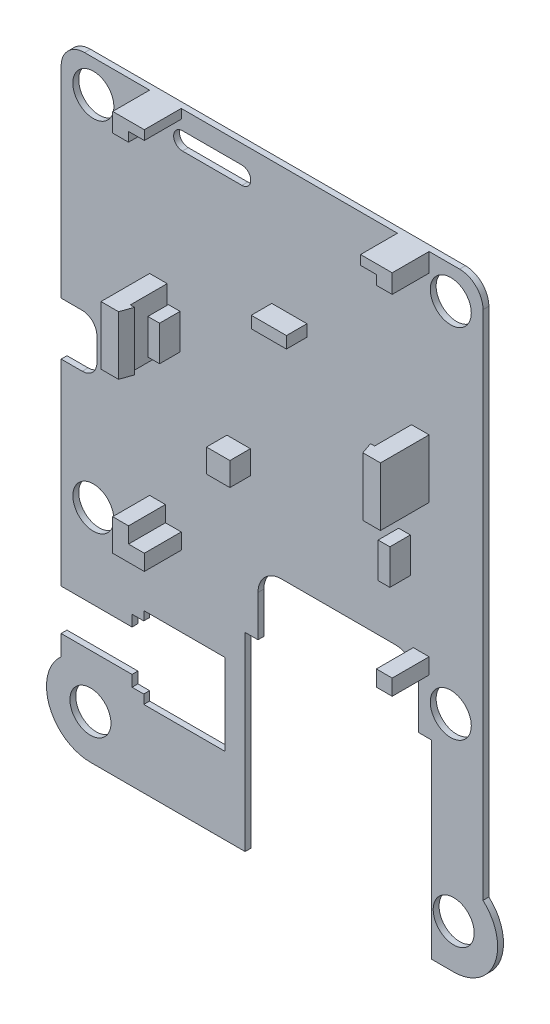
SolidWorks part; units mm, degrees
ref_plane "Front Plane" through (0, 0, 0) normal (0, 0, 1) x (1, 0, 0)
ref_plane "Top Plane" through (0, 0, 0) normal (0, 1, 0) x (1, 0, 0)
ref_plane "Right Plane" through (0, 0, 0) normal (1, 0, 0) x (0, 0, -1)
sketch "Sketch1" plane through (0, 0, 0) normal (0, 0, 1) x (1, 0, 0)
  line L9 (18, -18) -> (-18, -18)
  line L14 (16, 18) -> (-16, 18)
  line L15 (-18, 16) -> (-18, -1.15)
  line L16 (-18, -1.15) -> (-16.2, -1.15)
  line L17 (-14.95, -2.4) -> (-14.95, -4.4)
  line L18 (-16.2, -5.65) -> (-18, -5.65)
  line L19 (-18, -5.65) -> (-18, -18)
  line L20 (-18, -18) -> (-1.2, -18)
  line L21 (-1.2, -18) -> (-1.2, -14.5)
  line L22 (0.8, -12.5) -> (10.5, -12.5)
  line L23 (12.5, -14.5) -> (12.5, -18)
  line L24 (12.5, -18) -> (18, -18)
  line L25 (18, -18) -> (18, 16)
  line L26 (16, 18) -> (-16, 18)
  line L27 (-18, 16) -> (-18, -1.15)
  line L28 (-18, -1.15) -> (-16.2, -1.15)
  line L29 (-14.95, -2.4) -> (-14.95, -4.4)
  line L30 (-16.2, -5.65) -> (-18, -5.65)
  line L31 (-18, -5.65) -> (-18, -18)
  line L32 (-18, -18) -> (-1.2, -18)
  line L33 (-1.2, -18) -> (-1.2, -14.5)
  line L34 (0.8, -12.5) -> (10.5, -12.5)
  line L35 (12.5, -14.5) -> (12.5, -18)
  line L36 (12.5, -18) -> (18, -18)
  line L37 (18, -18) -> (18, 16)
  line L41 (13.6, -18) -> (13.6, -34.2)
  line L42 (13.6, -34.2) -> (15.5, -34.2)
  line L43 (18, -27.6549) -> (18, -18)
  line L44 (18, -18) -> (13.6, -18)
  line L46 (13.6, -18) -> (13.6, -34.2)
  line L47 (13.6, -34.2) -> (15.5, -34.2)
  line L48 (18, -27.6549) -> (18, -18)
  line L49 (18, -18) -> (13.6, -18)
  line L66 (-2.3, -18) -> (-18, -18)
  line L153 (-11.95, -22.43) -> (-11.95, -21.48)
  line L154 (-11.95, -21.48) -> (-10.95, -21.48)
  line L155 (-10.95, -21.48) -> (-10.95, -20.71)
  line L156 (-10.95, -20.71) -> (-4.01, -20.71)
  line L157 (-4.01, -20.71) -> (-4.01, -27.65)
  line L158 (-4.01, -27.65) -> (-10.95, -27.65)
  line L159 (-10.95, -27.65) -> (-10.95, -26.88)
  line L160 (-10.95, -26.88) -> (-11.95, -26.88)
  line L161 (-11.95, -26.88) -> (-11.95, -25.93)
  line L162 (-11.95, -25.93) -> (-18, -25.93)
  line L163 (-18, -25.93) -> (-18, -27.6549)
  line L164 (-15.5, -34.2) -> (-2.3, -34.2)
  line L165 (-2.3, -34.2) -> (-2.3, -18)
  line L166 (-2.3, -18) -> (-18, -18)
  line L167 (-18, -18) -> (-18, -22.43)
  line L168 (-18, -22.43) -> (-11.95, -22.43)
  line L169 (-11.95, -22.43) -> (-11.95, -21.48)
  line L170 (-11.95, -21.48) -> (-10.95, -21.48)
  line L171 (-10.95, -21.48) -> (-10.95, -20.71)
  line L172 (-10.95, -20.71) -> (-4.01, -20.71)
  line L173 (-4.01, -20.71) -> (-4.01, -27.65)
  line L174 (-4.01, -27.65) -> (-10.95, -27.65)
  line L175 (-10.95, -27.65) -> (-10.95, -26.88)
  line L176 (-10.95, -26.88) -> (-11.95, -26.88)
  line L177 (-11.95, -26.88) -> (-11.95, -25.93)
  line L178 (-11.95, -25.93) -> (-18, -25.93)
  line L179 (-18, -25.93) -> (-18, -27.6549)
  line L180 (-15.5, -34.2) -> (-2.3, -34.2)
  line L181 (-2.3, -34.2) -> (-2.3, -18)
  line L182 (-2.3, -18) -> (-18, -18)
  line L183 (-18, -18) -> (-18, -22.43)
  line L184 (-18, -22.43) -> (-11.95, -22.43)
  line L229 (-7.65, 14.9) -> (-2.57, 14.9) construction
  line L230 (-7.65, 16.4) -> (-2.57, 16.4) construction
  line L231 (-7.65, 16.4) -> (-2.57, 16.4)
  line L232 (-7.65, 14.9) -> (-2.57, 14.9)
  circle A2 centre (15.5, -30.45) radius 1.75 construction
  arc A3 (15.5, -34.2) -> (18, -27.6549) centre (15.5, -30.45) ccw
  circle A4 centre (15.25, -15.25) radius 1.75 construction
  circle A5 centre (15.25, 15.25) radius 1.75 construction
  circle A6 centre (-15.25, -15.25) radius 1.75 construction
  arc A7 (-16, 18) -> (-18, 16) centre (-16, 16) ccw
  arc A8 (-14.95, -2.4) -> (-16.2, -1.15) centre (-16.2, -2.4) ccw
  arc A9 (-16.2, -5.65) -> (-14.95, -4.4) centre (-16.2, -4.4) ccw
  arc A10 (0.8, -12.5) -> (-1.2, -14.5) centre (0.8, -14.5) ccw
  arc A11 (12.5, -14.5) -> (10.5, -12.5) centre (10.5, -14.5) ccw
  arc A12 (18, 16) -> (16, 18) centre (16, 16) ccw
  arc A14 (-16, 18) -> (-18, 16) centre (-16, 16) ccw
  arc A15 (-14.95, -2.4) -> (-16.2, -1.15) centre (-16.2, -2.4) ccw
  arc A16 (-16.2, -5.65) -> (-14.95, -4.4) centre (-16.2, -4.4) ccw
  arc A17 (0.8, -12.5) -> (-1.2, -14.5) centre (0.8, -14.5) ccw
  arc A19 (12.5, -14.5) -> (10.5, -12.5) centre (10.5, -14.5) ccw
  arc A20 (18, 16) -> (16, 18) centre (16, 16) ccw
  circle A21 centre (-15.25, 15.25) radius 1.75 construction
  arc A22 (15.5, -34.2) -> (18, -27.6549) centre (15.5, -30.45) ccw
  circle A23 centre (15.25, -15.25) radius 1.75
  circle A24 centre (15.25, 15.25) radius 1.75
  circle A25 centre (-15.25, -15.25) radius 1.75
  circle A26 centre (-15.25, 15.25) radius 1.75
  arc A27 (-18, -27.6549) -> (-15.5, -34.2) centre (-15.5, -30.45) ccw
  arc A28 (-18, -27.6549) -> (-15.5, -34.2) centre (-15.5, -30.45) ccw
  circle A36 centre (15.5, -30.45) radius 1.75
  circle A54 centre (-15.5, -30.45) radius 1.75 construction
  circle A57 centre (-15.5, -30.45) radius 1.75
  arc A62 (-2.57, 14.9) -> (-2.57, 16.4) centre (-2.57, 15.65) ccw construction
  arc A63 (-7.65, 16.4) -> (-7.65, 14.9) centre (-7.65, 15.65) ccw construction
  arc A64 (-7.65, 16.4) -> (-7.65, 14.9) centre (-7.65, 15.65) ccw
  arc A65 (-2.57, 14.9) -> (-2.57, 16.4) centre (-2.57, 15.65) ccw
  circle A69 centre (-15.5, -30.45) radius 1.75
  circle A70 centre (15.5, -30.45) radius 1.75
  dimension "D1" = 0
  dimension "D2" = 0
  dimension "D3" = 0
extrude "Base shape" add sketch "Sketch1" along normal blind 0.5 contours L37 A20 L26 A14 L27 L28 A15 L29 A16 L30 L31 L32 L33 A17 L34 A19 L35 L36 A26 A25 A24 A23 | L36 | L32 | L47 A22 L48 L9 L46 A36 region at (16.0251, -25.6944, 0) region at (-0.1312, 0.8573, 0) region at (-2.5345, -26.1, 0)
sketch "Sketch2" plane through (0, 0, 0.5) normal (0, 0, 1) x (1, 0, 0)
  line L0 (1.475, 16.95) -> (1.475, -13.05) construction
  line L1 (-7.85, 1.45) -> (-8.85, 1.45) construction
  line L2 (-0.025, 7.45) -> (2.975, 7.45)
  line L3 (-0.025, 7.45) -> (-0.025, 6.45)
  line L4 (11.8, 16.95) -> (-8.85, 16.95)
  line L5 (-8.85, 16.95) -> (-8.85, -13.05)
  line L6 (-8.85, -13.05) -> (11.8, -13.05)
  line L7 (11.8, -13.05) -> (11.8, 16.95)
  line L8 (11.8, 16.95) -> (-8.85, 16.95)
  line L9 (-8.85, 16.95) -> (-8.85, -13.05)
  line L10 (-8.85, -13.05) -> (11.8, -13.05)
  line L11 (11.8, -13.05) -> (11.8, 16.95)
  line L12 (-0.025, 6.45) -> (2.975, 6.45)
  line L13 (2.975, 7.45) -> (2.975, 6.45)
  line L14 (-0.025, 7.45) -> (2.975, 6.45) construction
  line L15 (-0.025, 6.45) -> (2.975, 7.45) construction
  line L16 (-8.85, 2.95) -> (-7.85, 2.95)
  line L17 (-8.85, 2.95) -> (-8.85, -0.05)
  line L18 (-8.85, -0.05) -> (-7.85, -0.05)
  line L19 (-7.85, 2.95) -> (-7.85, -0.05)
  line L20 (-3.85, -4.2) -> (-1.85, -4.2)
  line L21 (-3.85, -4.2) -> (-3.85, -6.2)
  line L22 (-3.85, -6.2) -> (-1.85, -6.2)
  line L23 (-1.85, -4.2) -> (-1.85, -6.2)
  line L24 (11.8, -3.75) -> (10.8, -3.75)
  line L25 (11.8, -3.75) -> (11.8, -6.75)
  line L26 (11.8, -6.75) -> (10.8, -6.75)
  line L27 (10.8, -3.75) -> (10.8, -6.75)
  line L28 (11.8, 1.95) -> (10.8, 1.95)
  line L29 (11.8, 1.95) -> (11.8, -1.05)
  line L30 (11.8, -1.05) -> (10.8, -1.05)
  line L31 (10.8, 1.95) -> (10.8, -1.05)
  line L32 (-3.85, -5.2) -> (-1.85, -5.2) construction
  line L33 (-2.85, -4.2) -> (-2.85, -6.2) construction
  line L34 (10.8, 0.45) -> (11.8, 0.45) construction
  line L35 (10.8, -5.25) -> (11.8, -5.25) construction
  point P6 (1.475, 6.95)
  dimension "D2" = 3
  dimension "D3" = 1
  dimension "D4" = 10
  dimension "D5" = 7.8
  dimension "D6" = 16.5
  dimension "D7" = 7.85
  dimension "D8" = 6
  dimension "D9" = 2
  dimension "D10" = 15.5
  dimension "D1" = 0
extrude "RX supports" add sketch "Sketch2" along normal blind 1.75 contours L13 L2 L3 L12 | L19 L16 L9 L18 | L23 L20 L21 L22 | L28 L31 L30 L11 | L24 L27 L26 L11 region at (1.475, 6.95, 0.5) region at (11.3, 0.45, 0.5) region at (-8.35, 1.45, 0.5) region at (11.3, -5.25, 0.5) region at (-2.85, -5.2, 0.5)
sketch "Sketch3" plane through (0, 0, 0.5) normal (0, 0, 1) x (1, 0, 0)
  line L0 (-8.85, 1.95) -> (11.8, 1.95) construction
  line L1 (1.475, 16.95) -> (1.475, -13.05) construction
  line L2 (-8.95, 4.45) -> (-10.45, 4.45)
  line L3 (-8.95, 4.45) -> (-8.95, -0.55)
  line L4 (11.8, 16.95) -> (-8.85, 16.95)
  line L5 (-8.85, 16.95) -> (-8.85, -13.05)
  line L6 (-8.85, -13.05) -> (11.8, -13.05)
  line L7 (11.8, -13.05) -> (11.8, 16.95)
  line L8 (11.8, 16.95) -> (-8.85, 16.95)
  line L9 (-8.85, 16.95) -> (-8.85, -13.05)
  line L10 (-8.85, -13.05) -> (11.8, -13.05)
  line L11 (11.8, -13.05) -> (11.8, 16.95)
  line L12 (-8.95, -0.55) -> (-10.45, -0.55)
  line L13 (-10.45, 4.45) -> (-10.45, -0.55)
  line L14 (11.9, -0.55) -> (13.4, -0.55)
  line L15 (13.4, 4.45) -> (13.4, -0.55)
  line L16 (11.9, 4.45) -> (13.4, 4.45)
  line L17 (11.9, 4.45) -> (11.9, -0.55)
  point P10 (-10.45, 1.95)
  dimension "D2" = 5
  dimension "D3" = 1.5
  dimension "D4" = 0.1
  dimension "D1" = 0
extrude "Clip base" add sketch "Sketch3" along normal offset from surface (3.15 mm away) 0.2 contours L2 L13 L12 L3 | L16 L17 L14 L15 region at (-9.7, 1.95, 0.5) region at (12.65, 1.95, 0.5) offset beyond the face yes
sketch "Sketch4" plane through (0, 0, 3.65) normal (0, 0, 1) x (1, 0, 0)
  line L0 (-8.95, -0.55) -> (-10.45, -0.55) construction
  line L1 (-10.45, 4.45) -> (-8.6, 4.45)
  line L2 (-10.45, 4.45) -> (-10.45, -0.55)
  line L3 (-10.45, -0.55) -> (-8.6, -0.55)
  line L4 (-8.6, 4.45) -> (-8.6, -0.55)
  line L5 (-8.95, 4.45) -> (-8.95, -0.55) construction
  line L6 (-10.45, 1.95) -> (13.4, 1.95) construction
  line L7 (13.4, 4.45) -> (13.4, -0.55) construction
  line L8 (1.475, 4.45) -> (1.475, -0.55) construction
  line L9 (11.55, 4.45) -> (11.55, -0.55)
  line L10 (13.4, 4.45) -> (11.55, 4.45)
  line L11 (13.4, 4.45) -> (13.4, -0.55)
  line L12 (13.4, -0.55) -> (11.55, -0.55)
  point P17 (1.475, 1.95)
  dimension "D1" = 0.35
extrude "Clip top" add sketch "Sketch4" along normal blind 1
sketch "Sketch5" plane through (0, -0.55, 0) normal (0, -1, 0) x (1, 0, 0)
  line L0 (-8.6, 3.65) -> (-8.95, 4.65)
  line L1 (-10.45, 4.65) -> (-8.6, 4.65) construction
  line L2 (-8.95, 4.65) -> (-8.6, 4.65)
  line L3 (-8.6, 4.65) -> (-8.6, 3.65)
  line L4 (-8.95, 3.65) -> (-8.95, 0.5) construction
  line L5 (11.55, 3.65) -> (11.9, 4.65)
  line L6 (11.55, 4.65) -> (13.4, 4.65) construction
  line L7 (11.9, 4.65) -> (11.55, 4.65)
  line L8 (11.55, 4.65) -> (11.55, 3.65)
  line L9 (11.9, 3.65) -> (11.9, 0.5) construction
extrude "Clip chamfer" cut sketch "Sketch5" against normal up to next
sketch "Sketch6" plane through (0, 0, 0.5) normal (0, 0, 1) x (1, 0, 0)
  line L0 (-10.45, 4.45) -> (-10.45, -0.55) construction
  line L1 (13.4, 4.45) -> (13.4, -0.55) construction
  line L2 (10.7, 18) -> (13.4, 18)
  line L3 (10.7, 18) -> (10.7, 16.4)
  line L4 (10.7, 16.4) -> (13.4, 16.4)
  line L5 (-7.75, -14.65) -> (-10.45, -14.65)
  line L6 (-7.75, -14.65) -> (-7.75, -11.95)
  line L7 (-7.75, -11.95) -> (-10.45, -11.95)
  line L8 (-9.1, -13.3) -> (12.05, -13.3)
  line L9 (12.05, -13.3) -> (12.05, 17.2)
  line L10 (12.05, 17.2) -> (-9.1, 17.2)
  line L11 (-9.1, 17.2) -> (-9.1, -13.3)
  line L12 (-9.1, -13.3) -> (12.05, -13.3)
  line L13 (12.05, -13.3) -> (12.05, 17.2)
  line L14 (12.05, 17.2) -> (-9.1, 17.2)
  line L15 (-9.1, 17.2) -> (-9.1, -13.3)
  line L16 (-10.45, -14.65) -> (-10.45, -11.95)
  line L17 (-7.75, -14.65) -> (-10.45, -11.95) construction
  line L18 (-7.75, -11.95) -> (-10.45, -14.65) construction
  line L19 (13.4, 18) -> (13.4, 16.4)
  line L20 (10.7, 18) -> (13.4, 16.4) construction
  line L21 (10.7, 16.4) -> (13.4, 18) construction
  line L22 (16, 18) -> (-16, 18) construction
  line L23 (-10.45, 4.45) -> (-10.45, -0.55) construction
  line L24 (-10.45, 16.4) -> (-7.75, 16.4)
  line L25 (-10.45, 16.4) -> (-10.45, 18)
  line L26 (-10.45, 18) -> (-7.75, 18)
  line L27 (-7.75, 16.4) -> (-7.75, 18)
  line L28 (-10.45, 16.4) -> (-7.75, 18) construction
  line L29 (-10.45, 18) -> (-7.75, 16.4) construction
  line L31 (12.05, -13.3) -> (13.4, -13.3)
  line L32 (12.05, -13.3) -> (12.05, -11.95)
  line L33 (12.05, -11.95) -> (13.4, -11.95)
  line L34 (13.4, -13.3) -> (13.4, -11.95)
  dimension "D1" = 0.25
extrude "Boss-Extrude1" add sketch "Sketch6" along normal up to surface (3.15 mm away) contours L14 L27 L26 L25 L24 L15 | L19 L2 L3 L14 L13 L4 | L31 L34 L33 L13 | L16 L5 L6 L12 L15 L7 region at (12.275, 17.3333, 0.5) region at (-9.325, 17.3333, 0.5) region at (12.725, -12.625, 0.5) region at (-9.325, -13.525, 0.5) up to face at (-8.775, 1.95, 3.65)
